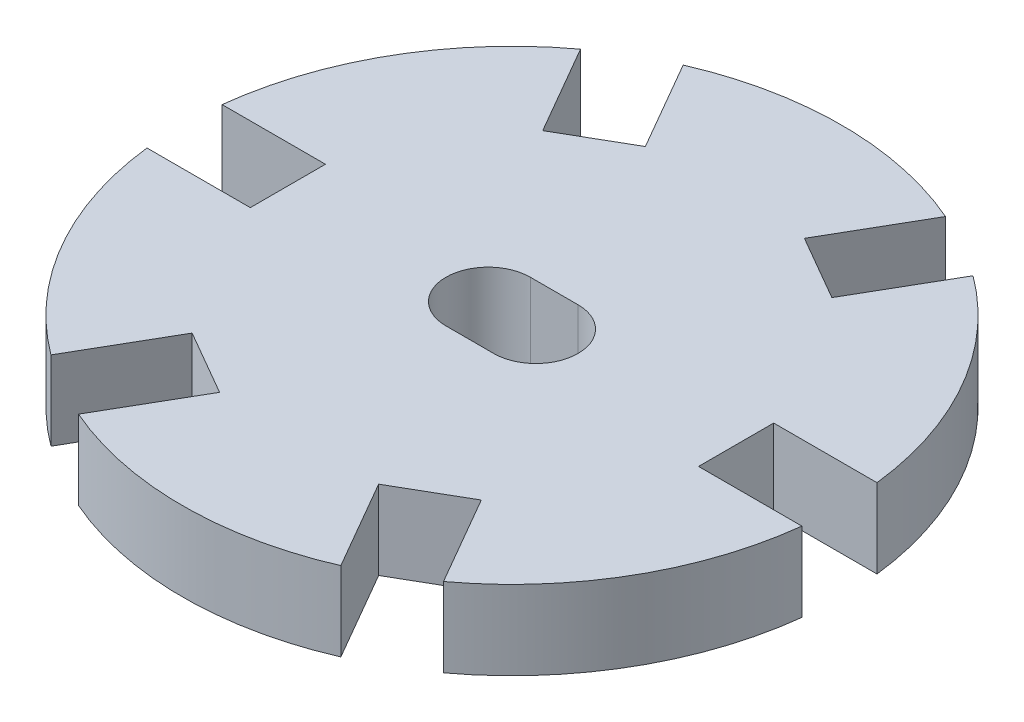
SolidWorks part; units mm, degrees
ref_plane "Front Plane" through (0, 0, 0) normal (0, 0, 1) x (1, 0, 0)
ref_plane "Top Plane" through (0, 0, 0) normal (0, 1, 0) x (1, 0, 0)
ref_plane "Right Plane" through (0, 0, 0) normal (1, 0, 0) x (0, 0, -1)
sketch "Sketch1" plane through (0, 0, 0) normal (0, 1, 0) x (1, 0, 0)
  circle A0 centre (0, 0) radius 12.5
  dimension "D1" = 25
extrude "Boss-Extrude1" add sketch "Sketch1" along normal blind 1.5 and the other way blind 1.5
sketch "Sketch2" plane through (0, 1.5, 0) normal (0, 1, 0) x (1, 0, 0)
  line L0 (9.4841, 13.5769) -> (5.4841, 6.6487)
  line L1 (16.5, -1.425) -> (8.5, -1.425)
  line L2 (16.5, -1.425) -> (16.5, 1.425)
  line L3 (16.5, 1.425) -> (8.5, 1.425)
  line L4 (8.5, -1.425) -> (8.5, 1.425)
  line L5 (12.5, 1.425) -> (12.5, -1.425) construction
  line L6 (16.5, 0) -> (8.5, 0) construction
  line L7 (9.4841, 13.5769) -> (7.0159, 15.0019)
  line L8 (7.0159, 15.0019) -> (3.0159, 8.0737)
  line L9 (5.4841, 6.6487) -> (3.0159, 8.0737)
  line L10 (5.0159, 11.5378) -> (7.4841, 10.1128) construction
  line L11 (8.25, 14.2894) -> (4.25, 7.3612) construction
  line L12 (-7.0159, 15.0019) -> (-3.0159, 8.0737)
  line L13 (-7.0159, 15.0019) -> (-9.4841, 13.5769)
  line L14 (-9.4841, 13.5769) -> (-5.4841, 6.6487)
  line L15 (-3.0159, 8.0737) -> (-5.4841, 6.6487)
  line L16 (-7.4841, 10.1128) -> (-5.0159, 11.5378) construction
  line L17 (-8.25, 14.2894) -> (-4.25, 7.3612) construction
  line L18 (-16.5, 1.425) -> (-8.5, 1.425)
  line L19 (-16.5, 1.425) -> (-16.5, -1.425)
  line L20 (-16.5, -1.425) -> (-8.5, -1.425)
  line L21 (-8.5, 1.425) -> (-8.5, -1.425)
  line L22 (-12.5, -1.425) -> (-12.5, 1.425) construction
  line L23 (-16.5, 0) -> (-8.5, 0) construction
  line L24 (-9.4841, -13.5769) -> (-5.4841, -6.6487)
  line L25 (-9.4841, -13.5769) -> (-7.0159, -15.0019)
  line L26 (-7.0159, -15.0019) -> (-3.0159, -8.0737)
  line L27 (-5.4841, -6.6487) -> (-3.0159, -8.0737)
  line L28 (-5.0159, -11.5378) -> (-7.4841, -10.1128) construction
  line L29 (-8.25, -14.2894) -> (-4.25, -7.3612) construction
  line L30 (7.0159, -15.0019) -> (3.0159, -8.0737)
  line L31 (7.0159, -15.0019) -> (9.4841, -13.5769)
  line L32 (9.4841, -13.5769) -> (5.4841, -6.6487)
  line L33 (3.0159, -8.0737) -> (5.4841, -6.6487)
  line L34 (7.4841, -10.1128) -> (5.0159, -11.5378) construction
  line L35 (8.25, -14.2894) -> (4.25, -7.3612) construction
  circle A0 centre (0, 0) radius 12.5 construction
  point P0 (12.5, 0)
  point P9 (6.25, 10.8253)
  point P18 (-6.25, 10.8253)
  point P27 (-12.5, 0)
  point P36 (-6.25, -10.8253)
  point P45 (6.25, -10.8253)
  point P54 (0, 0)
  dimension "D1" = 2.85
  dimension "D2" = 4
  dimension "D3" = 6
extrude "Cut-Extrude1" cut sketch "Sketch2" against normal through all
sketch "Sketch3" plane through (0, 0, 0) normal (0, 1, 0) x (1, 0, 0)
  line L2 (0.7055, 0) -> (-0.7055, 0) construction
  line L3 (0.7055, -1.6) -> (-0.7055, -1.6) construction
  line L4 (0.7055, 1.6) -> (-0.7055, 1.6) construction
  line L5 (-2.3055, 1.5) -> (-2.3055, -1.5) construction
  line L6 (-0.9055, 0) -> (0.9055, 0) construction
  line L7 (-0.9055, 1.6) -> (0.9055, 1.6)
  line L8 (-0.9055, -1.6) -> (0.9055, -1.6)
  arc A2 (0.7055, -1.6) -> (0.7055, 1.6) centre (0.7055, 0) ccw construction
  arc A3 (-0.7055, 1.6) -> (-0.7055, -1.6) centre (-0.7055, 0) ccw construction
  arc A4 (-0.9055, 1.6) -> (-0.9055, -1.6) centre (-0.9055, 0) ccw
  arc A5 (0.9055, -1.6) -> (0.9055, 1.6) centre (0.9055, 0) ccw
  point P2 (0, 0)
  point P11 (0, 0)
  dimension "D1" = 3.2
  dimension "D2" = 0.2
extrude "Cut-Extrude2" cut sketch "Sketch3" against normal through all both and the other way through all
